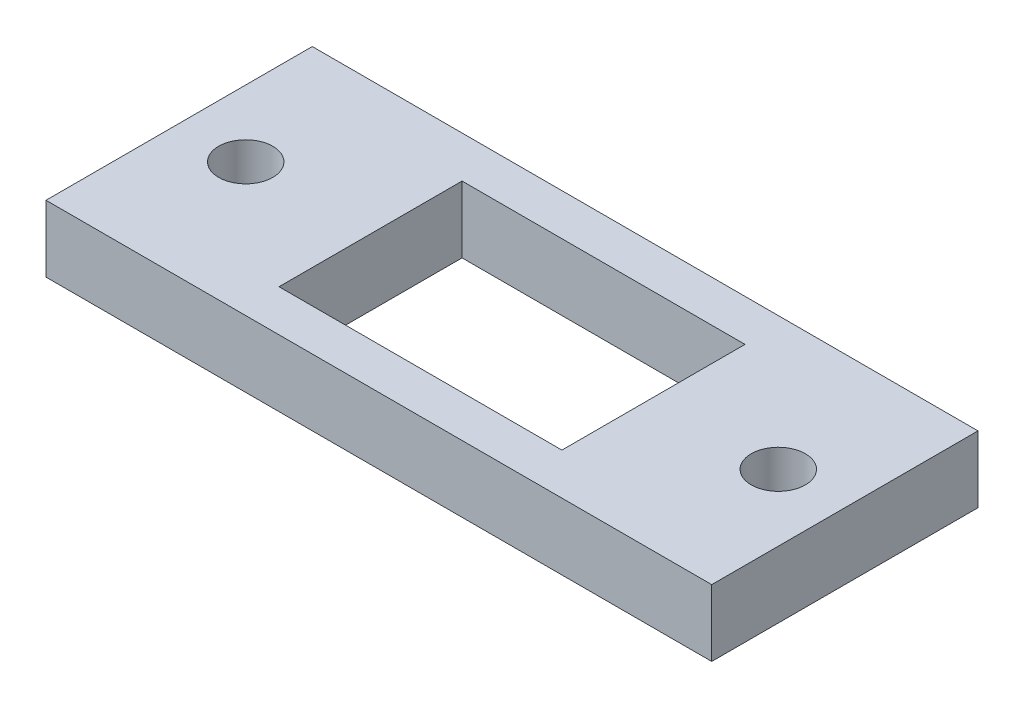
SolidWorks part; units mm, degrees
ref_plane "Front Plane" through (0, 0, 0) normal (0, 0, 1) x (1, 0, 0)
ref_plane "Top Plane" through (0, 0, 0) normal (0, 1, 0) x (1, 0, 0)
ref_plane "Right Plane" through (0, 0, 0) normal (1, 0, 0) x (0, 0, -1)
sketch "Sketch1" plane through (0, 0, 0) normal (0, 1, 0) x (1, 0, 0)
  line L0 (0, 50.8) -> (254, 50.8) construction
  line L1 (0, 0) -> (254, 0)
  line L2 (0, 0) -> (0, 101.6)
  line L3 (0, 101.6) -> (254, 101.6)
  line L4 (254, 0) -> (254, 101.6)
  line L5 (127, 85.725) -> (127, 15.875) construction
  line L6 (73.025, 85.725) -> (180.975, 85.725)
  line L7 (73.025, 85.725) -> (73.025, 15.875)
  line L8 (73.025, 15.875) -> (180.975, 15.875)
  line L9 (180.975, 85.725) -> (180.975, 15.875)
  line L10 (73.025, 50.8) -> (180.975, 50.8) construction
  line L11 (127, 101.6) -> (127, 0) construction
  circle A0 centre (25.4, 50.8) radius 10.3188
  circle A1 centre (228.6, 50.8) radius 10.3187
  dimension "D3" = 20.6375
  dimension "D4" = 25.4
  dimension "D5" = 25.4
  dimension "D1" = 101.6
  dimension "D2" = 254
  dimension "D6" = 107.95
  dimension "D7" = 69.85
extrude "Boss-Extrude1" add sketch "Sketch1" along normal blind 25.4
